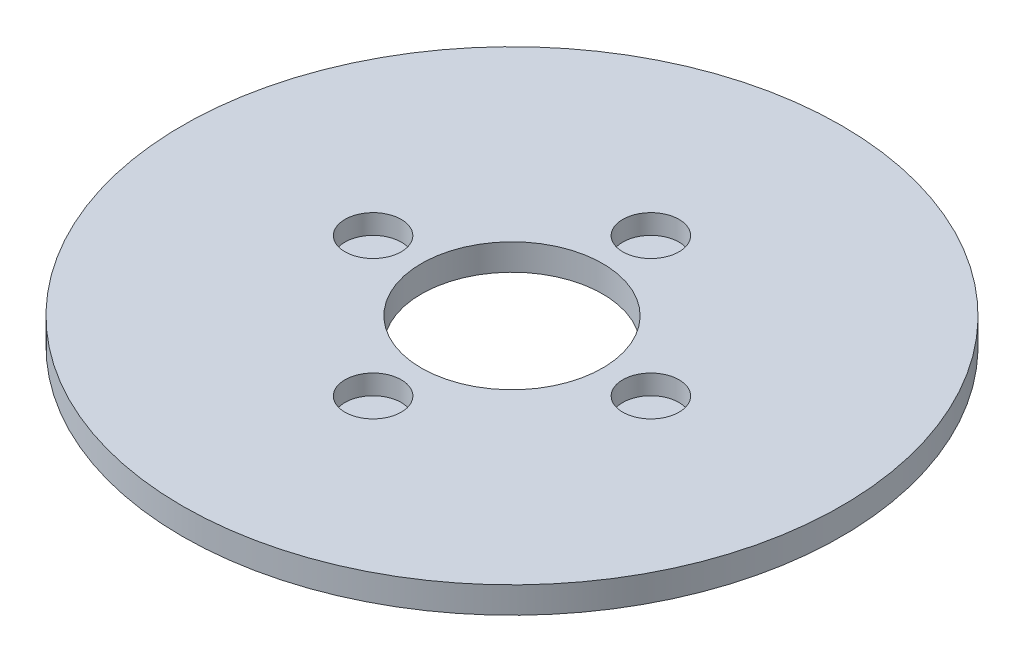
SolidWorks part; units mm, degrees
ref_plane "Front Plane" through (0, 0, 0) normal (0, 0, 1) x (1, 0, 0)
ref_plane "Top Plane" through (0, 0, 0) normal (0, 1, 0) x (1, 0, 0)
ref_plane "Right Plane" through (0, 0, 0) normal (1, 0, 0) x (0, 0, -1)
sketch "Sketch1" plane through (0, 0, 0) normal (0, 1, 0) x (1, 0, 0)
  circle A0 centre (0, 0) radius 100
  dimension "FLANGE_OD" = 200
extrude "Boss-Extrude1" add sketch "Sketch1" along normal blind 8
sketch "Sketch2" plane through (0, 0, 0) normal (0, 1, 0) x (1, 0, 0)
  circle A0 centre (0, 0) radius 27.5
  dimension "BORE_D" = 55
extrude "Cut-Extrude1" cut sketch "Sketch2" along normal through all
sketch "Sketch3" plane through (0, 8, 0) normal (0, 1, 0) x (1, 0, 0)
  circle A0 centre (0, 0) radius 42.1471 construction
  circle A1 centre (-42.1471, 0) radius 8.5357
  dimension "BOLT_D" = 17.0714
  dimension "BOLT_PCD" = 84.2942
extrude "Cut-Extrude2" cut sketch "Sketch3" against normal blind 5.9775
pattern_circular "CirPattern1" count 4 over 360 about axis through (0, 0, 0) along (0, 1, 0) of "Cut-Extrude2"
